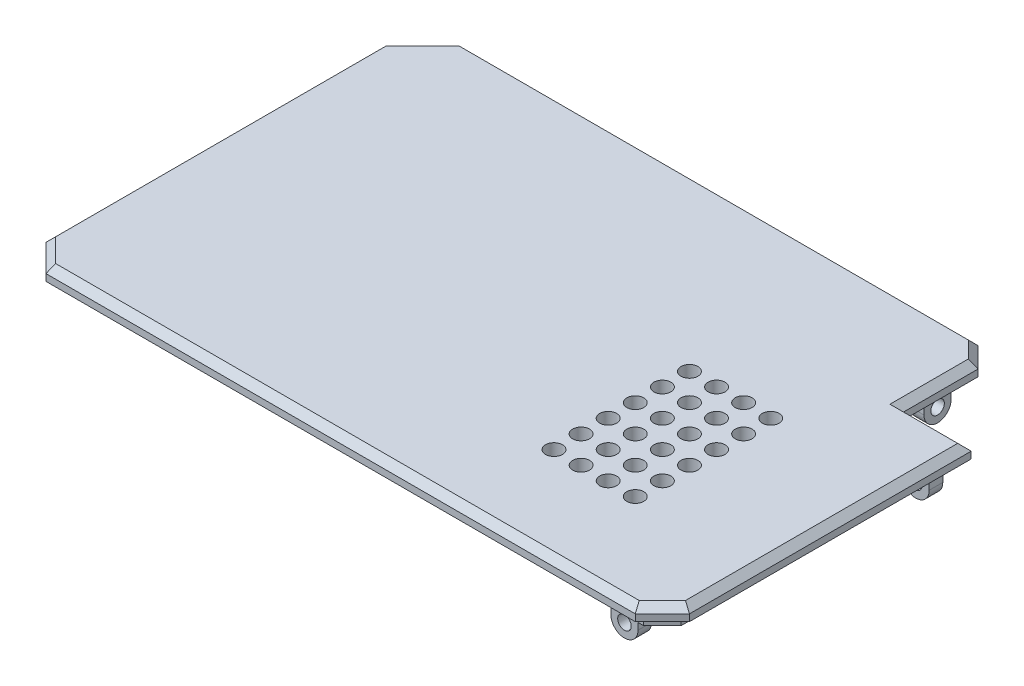
SolidWorks part; units mm, degrees
ref_plane "前视基准面" through (0, 0, 0) normal (0, 0, 1) x (1, 0, 0)
ref_plane "上视基准面" through (0, 0, 0) normal (0, 1, 0) x (1, 0, 0)
ref_plane "右视基准面" through (0, 0, 0) normal (1, 0, 0) x (0, 0, -1)
other "Configuration Table"
sketch "草图1" plane through (0, 0, 0) normal (0, 1, 0) x (1, 0, 0)
  line L3 (-10.9928, -16.6) -> (-6.9928, -12.6) construction
  line L4 (-10.9928, -16.6) -> (-97.9928, -16.6) construction
  line L5 (-101.9928, -12.6) -> (-97.9928, -16.6) construction
  line L10 (-16.9928, 40) -> (-16.9928, 29)
  line L11 (-16.9928, 29) -> (-6.9928, 29)
  line L12 (-6.9928, -12.6) -> (-6.9928, 29)
  line L13 (-10.9928, -16.6) -> (-6.9928, -12.6)
  line L14 (-10.9928, -16.6) -> (-97.9928, -16.6)
  line L15 (-101.9928, -12.6) -> (-97.9928, -16.6)
  line L16 (-101.9928, -12.6) -> (-101.9928, 37)
  line L17 (-95.9928, 43) -> (-101.9928, 37)
  line L18 (-19.9928, 43) -> (-95.9928, 43)
  line L19 (-16.9928, 40) -> (-19.9928, 43)
  point P2 (-101.9928, 37)
  point P7 (-95.9928, 43)
  point P8 (-19.9928, 43)
  point P11 (-16.9928, 40)
  point P12 (-16.9928, 29)
  point P14 (-6.9928, 29)
extrude "凸台-拉伸1" add sketch "草图1" along normal blind 2
sketch "草图2" plane through (0, 0, 0) normal (0, -1, 0) x (1, 0, 0)
  line L20 (-21.6911, -38.9) -> (-21.0928, -38.3017)
  line L21 (-21.0928, -38.3017) -> (-21.0928, -24.9)
  line L22 (-21.0928, -24.9) -> (-11.0928, -24.9)
  line L23 (-11.0928, -24.9) -> (-11.0928, 10.9017)
  line L24 (-11.0928, 10.9017) -> (-12.6911, 12.5)
  line L25 (-12.6911, 12.5) -> (-96.2945, 12.5)
  line L26 (-96.2945, 12.5) -> (-97.8928, 10.9017)
  line L27 (-97.8928, 10.9017) -> (-97.8928, -35.3017)
  line L28 (-97.8928, -35.3017) -> (-94.2945, -38.9)
  line L29 (-94.2945, -38.9) -> (-21.6911, -38.9)
  line L30 (-20.8626, -40.9) -> (-19.0928, -39.1302)
  line L31 (-19.0928, -39.1302) -> (-19.0928, -26.9)
  line L32 (-19.0928, -26.9) -> (-9.0928, -26.9)
  line L33 (-9.0928, -26.9) -> (-9.0928, 11.7302)
  line L34 (-9.0928, 11.7302) -> (-11.8626, 14.5)
  line L35 (-11.8626, 14.5) -> (-97.123, 14.5)
  line L36 (-97.123, 14.5) -> (-99.8928, 11.7302)
  line L37 (-99.8928, 11.7302) -> (-99.8928, -36.1302)
  line L38 (-99.8928, -36.1302) -> (-95.123, -40.9)
  line L39 (-95.123, -40.9) -> (-20.8626, -40.9)
  line L40 (-20.8626, -40.9) -> (-19.0928, -39.1302)
  line L41 (-19.0928, -39.1302) -> (-19.0928, -26.9)
  line L42 (-19.0928, -26.9) -> (-9.0928, -26.9)
  line L43 (-9.0928, -26.9) -> (-9.0928, 11.7302)
  line L44 (-9.0928, 11.7302) -> (-11.8626, 14.5)
  line L45 (-11.8626, 14.5) -> (-97.123, 14.5)
  line L46 (-97.123, 14.5) -> (-99.8928, 11.7302)
  line L47 (-99.8928, 11.7302) -> (-99.8928, -36.1302)
  line L48 (-99.8928, -36.1302) -> (-95.123, -40.9)
  line L49 (-95.123, -40.9) -> (-20.8626, -40.9)
  dimension "D1" = 2.1
  dimension "D2" = 2
extrude "凸台-拉伸2" add sketch "草图2" along normal blind 2
sketch "草图3" plane through (0, 2, 0) normal (0, 1, 0) x (1, 0, 0)
  line L0 (-6.9928, -12.6) -> (-6.9928, 29) construction
  line L1 (-97.9928, -16.6) -> (-10.9928, -16.6) construction
  circle A0 centre (-36.9928, -2.6) radius 1.25
  circle A1 centre (-32.9928, -2.6) radius 1.25
  circle A2 centre (-28.9928, -2.6) radius 1.25
  circle A3 centre (-24.9928, -2.6) radius 1.25
  circle A4 centre (-32.9928, 1.4) radius 1.25
  circle A5 centre (-28.9928, 1.4) radius 1.25
  circle A6 centre (-24.9928, 1.4) radius 1.25
  circle A7 centre (-32.9928, 5.4) radius 1.25
  circle A8 centre (-28.9928, 5.4) radius 1.25
  circle A9 centre (-24.9928, 5.4) radius 1.25
  circle A10 centre (-32.9928, 9.4) radius 1.25
  circle A11 centre (-28.9928, 9.4) radius 1.25
  circle A12 centre (-24.9928, 9.4) radius 1.25
  circle A13 centre (-36.9928, 1.4) radius 1.25
  circle A14 centre (-36.9928, 5.4) radius 1.25
  circle A15 centre (-36.9928, 9.4) radius 1.25
  circle A16 centre (-36.9928, 13.4) radius 1.25
  circle A17 centre (-32.9928, 13.4) radius 1.25
  circle A18 centre (-28.9928, 13.4) radius 1.25
  circle A19 centre (-24.9928, 13.4) radius 1.25
  circle A20 centre (-36.9928, 17.4) radius 1.25
  circle A21 centre (-32.9928, 17.4) radius 1.25
  circle A22 centre (-28.9928, 17.4) radius 1.25
  circle A23 centre (-24.9928, 17.4) radius 1.25
  dimension "D1" = 2.5
  dimension "D2" = 30
  dimension "D3" = 14
  dimension "D4" = 4
  dimension "D5" = 6
extrude "切除-拉伸1" cut sketch "草图3" against normal up to next
sketch "草图4" plane through (0, -2, 0) normal (0, -1, 0) x (1, 0, 0)
  line L0 (-97.8928, 10.9017) -> (-97.8928, -35.3017) construction
  line L1 (-94.2945, -38.9) -> (-90.2945, -38.9)
  line L2 (-94.2945, -38.9) -> (-94.2945, -40.9)
  line L3 (-94.2945, -40.9) -> (-90.2945, -40.9)
  line L4 (-90.2945, -38.9) -> (-90.2945, -40.9)
  line L5 (-21.0928, -24.9) -> (-11.0928, -24.9) construction
  line L6 (-19.0928, -34.1272) -> (-21.0928, -34.1272)
  line L7 (-19.0928, -34.1272) -> (-19.0928, -38.1272)
  line L8 (-19.0928, -38.1272) -> (-21.0928, -38.1272)
  line L9 (-21.0928, -34.1272) -> (-21.0928, -38.1272)
  line L10 (-100.9928, 8.6) -> (-104.6576, 8.6) construction
  line L11 (-9.0928, -26.9) -> (-13.0928, -26.9)
  line L12 (-9.0928, -26.9) -> (-9.0928, -24.9)
  line L13 (-9.0928, -24.9) -> (-13.0928, -24.9)
  line L14 (-13.0928, -26.9) -> (-13.0928, -24.9)
  line L16 (-12.6911, 12.5) -> (-16.6911, 12.5)
  line L17 (-12.6911, 12.5) -> (-12.6911, 14.5)
  line L18 (-12.6911, 14.5) -> (-16.6911, 14.5)
  line L19 (-16.6911, 12.5) -> (-16.6911, 14.5)
  line L21 (-99.8928, 6.6) -> (-97.8928, 6.6)
  line L22 (-99.8928, 6.6) -> (-99.8928, 10.6)
  line L23 (-99.8928, 10.6) -> (-97.8928, 10.6)
  line L24 (-97.8928, 6.6) -> (-97.8928, 10.6)
  line L25 (-19.0928, -39.1302) -> (-19.0928, -26.9) construction
  line L26 (-95.123, -40.9) -> (-20.8626, -40.9) construction
  line L27 (-99.8928, 11.7302) -> (-99.8928, -36.1302) construction
  line L28 (-97.8928, -35) -> (-99.8928, -35)
  line L29 (-97.8928, -35) -> (-97.8928, -31)
  line L30 (-97.8928, -31) -> (-99.8928, -31)
  line L31 (-99.8928, -35) -> (-99.8928, -31)
  line L32 (-100.9928, -33) -> (-104.0952, -33) construction
  line L33 (-11.8626, 14.5) -> (-97.123, 14.5) construction
  line L34 (-17.9928, -36.1272) -> (-12.8761, -36.1272) construction
  point P6 (-99.8928, 8.6)
  point P36 (-97.8928, -33)
  point P41 (-21.0928, -36.1272)
  dimension "D1" = 4
  dimension "D2" = 4
  dimension "D3" = 4
  dimension "D4" = 4
  dimension "D5" = 4
extrude "凸台-拉伸3" add sketch "草图4" along normal blind 3
fillet "圆角1" radius 2 12 edges at (-16.6911, -5, 13.5) (-12.6911, -5, 13.5) (-9.0928, -5, -25.9) (-13.0928, -5, -25.9) (-20.0928, -5, -38.1272) (-20.0928, -5, -34.1272) (-94.2945, -5, -39.9) (-90.2945, -5, -39.9) (-98.8928, -5, 10.6) (-98.8928, -5, 6.6) (-98.8928, -5, -35) (-98.8928, -5, -31)
sketch "草图5" plane through (0, 0, -26.9) normal (0, 0, -1) x (-1, 0, 0)
  circle A0 centre (11.0928, -3) radius 1
  dimension "D1" = 2
extrude "切除-拉伸2" cut sketch "草图5" against normal up to next (2 mm away) draft 2
sketch "草图6" plane through (0, 0, 14.5) normal (0, 0, 1) x (1, 0, 0)
  circle A0 centre (-14.6911, -3) radius 1
  dimension "D1" = 2
extrude "切除-拉伸3" cut sketch "草图6" against normal up to next (2 mm away) draft 2
sketch "草图7" plane through (-99.8928, 0, 0) normal (-1, 0, 0) x (0, 0, 1)
  circle A0 centre (8.6, -2.85) radius 1
  circle A2 centre (-33, -2.85) radius 1
  point P2 (-33, -2.85)
  dimension "D1" = 2
extrude "切除-拉伸4" cut sketch "草图7" against normal up to next (2 mm away) draft 2
sketch "草图8" plane through (0, 0, -40.9) normal (0, 0, -1) x (-1, 0, 0)
  circle A0 centre (92.2945, -3) radius 1
  dimension "D1" = 2
extrude "切除-拉伸5" cut sketch "草图8" against normal up to next (2 mm away) draft 2
sketch "草图9" plane through (-19.0928, 0, 0) normal (1, 0, 0) x (0, 0, -1)
  circle A1 centre (36.1302, -3) radius 1
  point P2 (0, 0)
  dimension "D1" = 2
extrude "切除-拉伸6" cut sketch "草图9" against normal up to next (2 mm away) draft 2
sketch "草图10" plane through (0, 0, 0) normal (0, -1, 0) x (1, 0, 0)
  line L0 (-19.9928, -43) -> (-95.9928, -43) construction
  line L1 (-71.9928, -29) -> (-69.9928, -29)
  line L2 (-71.9928, -29) -> (-71.9928, -21)
  line L3 (-71.9928, -21) -> (-69.9928, -21)
  line L4 (-69.9928, -29) -> (-69.9928, -21)
  line L5 (-49.9928, -29) -> (-47.9928, -29)
  line L6 (-49.9928, -29) -> (-49.9928, -21)
  line L7 (-49.9928, -21) -> (-47.9928, -21)
  line L8 (-47.9928, -29) -> (-47.9928, -21)
  line L9 (-101.9928, -37) -> (-101.9928, 12.6) construction
  dimension "D1" = 2
  dimension "D2" = 2
  dimension "D3" = 14
  dimension "D4" = 8
  dimension "D5" = 30
  dimension "D6" = 20
extrude "凸台-拉伸4" add sketch "草图10" along normal blind 2.85
sketch "草图11" plane through (0, -2.85, 0) normal (0, -1, 0) x (1, 0, 0)
  line L1 (-71.9928, -29) -> (-69.9928, -29)
  line L2 (-71.9928, -29) -> (-71.9928, -26.75)
  line L3 (-71.9928, -26.75) -> (-69.9928, -26.75)
  line L4 (-69.9928, -29) -> (-69.9928, -26.75)
  line L5 (-49.9928, -29) -> (-47.9928, -29)
  line L6 (-49.9928, -29) -> (-49.9928, -26.75)
  line L7 (-49.9928, -26.75) -> (-47.9928, -26.75)
  line L8 (-47.9928, -29) -> (-47.9928, -26.75)
  line L10 (-69.9928, -29) -> (-69.9928, -21) construction
  line L11 (-47.9928, -29) -> (-47.9928, -21) construction
  dimension "D1" = 2.25
extrude "凸台-拉伸5" add sketch "草图11" along normal blind 2
chamfer "倒角1" distance 1 angle 35 2 edges at (-48.9928, -4.85, -26.75) (-70.9928, -4.85, -26.75) first distance on face at (-48.9928, -3.85, -26.75) first distance on face at (-70.9928, -3.85, -26.75)
sketch "草图12" plane through (0, 0, 0) normal (0, -1, 0) x (1, 0, 0)
  line L1 (-20.9928, -2.1) -> (-18.9928, -2.1)
  line L2 (-20.9928, -2.1) -> (-20.9928, -6.9)
  line L3 (-20.9928, -6.9) -> (-18.9928, -6.9)
  line L4 (-18.9928, -2.1) -> (-18.9928, -6.9)
  line L5 (-97.9928, 16.6) -> (-10.9928, 16.6) construction
  line L6 (-6.9928, 12.6) -> (-6.9928, -29) construction
  dimension "D1" = 2
  dimension "D2" = 4.8
  dimension "D3" = 12
  dimension "D4" = 18.7
extrude "凸台-拉伸6" add sketch "草图12" along normal blind 7
chamfer "倒角2" distance 1 angle 35 1 edges at (-19.9928, -7, -6.9) first distance on face at (-19.9928, -3.5, -6.9)
sketch "草图13" plane through (0, 0, 0) normal (0, -1, 0) x (1, 0, 0)
  line L1 (-99.8928, -21.4) -> (-96.9928, -21.4)
  line L2 (-99.8928, -21.4) -> (-99.8928, -27.4)
  line L3 (-99.8928, -27.4) -> (-96.9928, -27.4)
  line L4 (-96.9928, -21.4) -> (-96.9928, -27.4)
  line L7 (-99.8928, 6.6) -> (-99.8928, -31) construction
  dimension "D1" = 2.9
extrude "凸台-拉伸7" add sketch "草图13" along normal blind 7
chamfer "倒角3" distance 1 angle 35 1 edges at (-96.9928, -7, -24.4) first distance on face at (-96.9928, -3.5, -24.4)
chamfer "倒角4" distance 1 angle 45 10 edges at (-99.9928, 2, 14.6) (-101.9928, 2, -12.2) (-98.9928, 2, -40) (-57.9928, 2, -43) (-18.4928, 2, -41.5) (-16.9928, 2, -34.5) (-11.9928, 2, -29) (-6.9928, 2, -8.2) (-54.4928, 2, 16.6) (-8.9928, 2, 14.6)
